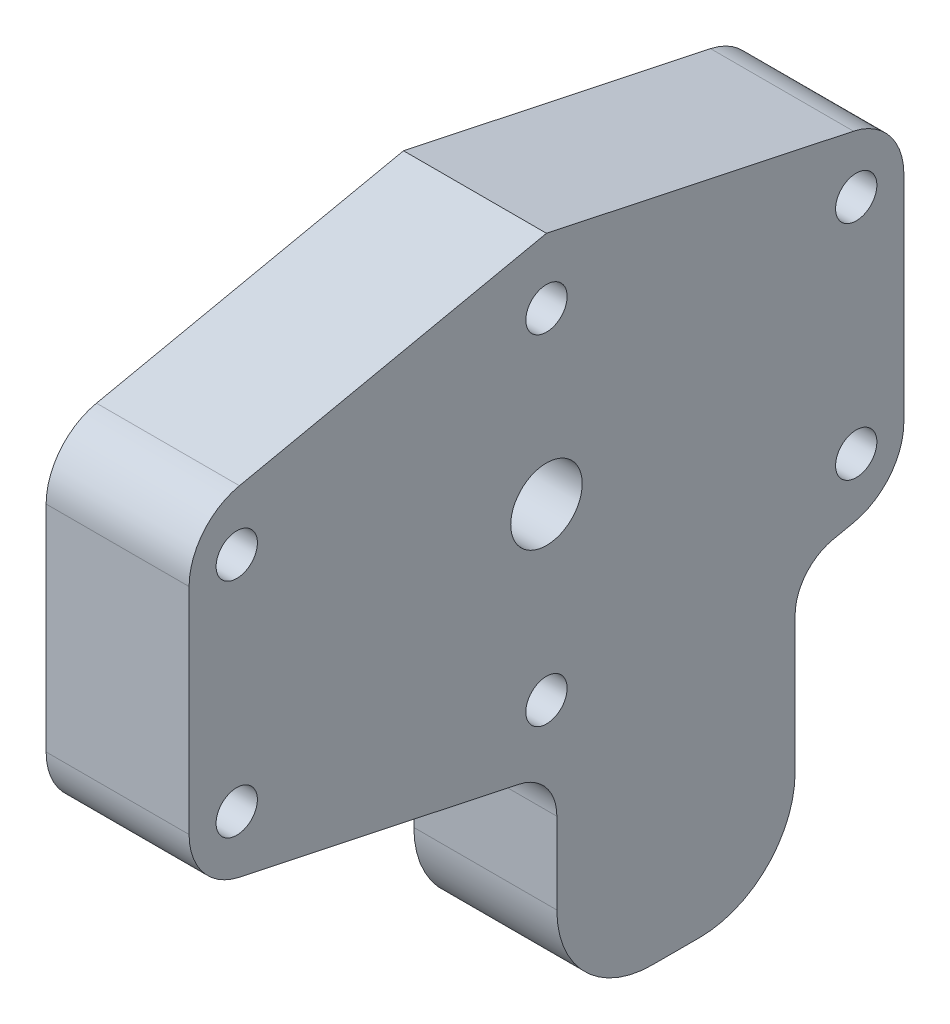
SolidWorks part; units mm, degrees
ref_plane "Front" through (0, 0, 0) normal (0, 0, 1) x (1, 0, 0)
ref_plane "Top" through (0, 0, 0) normal (0, 1, 0) x (1, 0, 0)
ref_plane "Right" through (0, 0, 0) normal (1, 0, 0) x (0, 0, -1)
sketch "Sketch1" plane through (0, 0, 0) normal (1, 0, 0) x (0, 0, -1)
  line L0 (0, -20) -> (22.5, -24.7697)
  line L1 (0, 0) -> (45, 0)
  line L2 (0, 0) -> (0, -20)
  line L3 (0, -20) -> (45, -20)
  line L4 (45, 0) -> (45, -20)
  line L5 (22.5, -24.7697) -> (45, -20)
  line L6 (22.5, 4.7697) -> (0, 0)
  line L7 (22.5, 4.7697) -> (45, 0)
  circle A0 centre (22.5, -20.6808) radius 1.3
  circle A1 centre (22.5, 0.6808) radius 1.3
  circle A2 centre (42, -17) radius 1.3
  circle A3 centre (3, -17) radius 1.3
  circle A4 centre (3, -3) radius 1.3
  circle A5 centre (42, -3) radius 1.3
  dimension "D7" = 2.6
  dimension "D8" = 2.6
  dimension "D13" = 2.6
  dimension "D1" = 45
  dimension "D2" = 20
  dimension "D3" = 23
  dimension "D4" = 23
  dimension "D5" = 23
  dimension "D6" = 23
  dimension "D9" = 4
  dimension "D10" = 4
  dimension "D11" = 4
  dimension "D12" = 4
  dimension "D14" = 3
  dimension "D15" = 3
  dimension "D16" = 2
  dimension "D17" = 2
extrude "Boss-Extrude1" add sketch "Sketch1" along normal blind 9 contours L7 L6 L1 A1 | L4 L1 L2 L3 | L0 L5 L3 A0 region at (0, -20.4525, -10.6963) region at (0, -10, -22.5) region at (0, 1.9422, -11.3438)
sketch "Sketch7" plane through (0, 0, 0) normal (-1, 0, 0) x (0, 0, 1)
  line L0 (-41.7, -10) -> (-31.3, -10)
  line L1 (-45, 0) -> (-45, -20) construction
  line L2 (-13.7, -10) -> (-3.3, -10)
  arc A0 (-31.3, -10) -> (-41.7, -10) centre (-36.5, -10) ccw
  arc A1 (-3.3, -10) -> (-13.7, -10) centre (-8.5, -10) ccw
  dimension "D1" = 10.4
  dimension "D2" = 8.5
  dimension "D3" = 10
  dimension "D4" = 2
revolve "Cut-Revolve3" cut sketch "Sketch7" angle 180 about L0 reverse direction yes
sketch "Sketch8" plane through (0, 0, 0) normal (-1, 0, 0) x (0, 0, 1)
  circle A0 centre (-22.5, -10) radius 8.1
  dimension "D1" = 16.2
  dimension "D2" = 22.5
  dimension "D3" = 10
extrude "Cut-Extrude4" cut sketch "Sketch8" against normal blind 5.5
sketch "Sketch9" plane through (5.5, 0, 0) normal (-1, 0, 0) x (0, 0, 1)
  circle A0 centre (-22.5, -10) radius 2.25
  dimension "D1" = 4.5
extrude "Cut-Extrude5" cut sketch "Sketch9" against normal through all
sketch "Sketch16" plane through (9, 0, 0) normal (1, 0, 0) x (0, 0, -1)
  line L0 (38.1522, -21.4516) -> (38.1522, -38.4516)
  line L1 (22.5, -24.7697) -> (45, -20) construction
  line L2 (38.1522, -38.4516) -> (23.1522, -38.4516)
  line L3 (23.1522, -38.4516) -> (23.1522, -24.6314)
  line L4 (23.1522, -24.6314) -> (38.1522, -21.4516)
  dimension "D1" = 17
  dimension "D2" = 15
  dimension "D3" = 7
extrude "Boss-Extrude7" add sketch "Sketch16" against normal blind 9
sketch "Sketch17" plane through (0, 0, 0) normal (-1, 0, 0) x (0, 0, 1)
  line L0 (-38.1522, -38.4516) -> (-38.1522, -21.4516) construction
  line L1 (-23.1522, -38.4516) -> (-38.1522, -38.4516) construction
  line L2 (-25.4522, -30.4516) -> (-35.8522, -30.4516)
  arc A0 (-25.4522, -30.4516) -> (-35.8522, -30.4516) centre (-30.6522, -30.4516) ccw
  dimension "D1" = 10.4
  dimension "D2" = 7.5
  dimension "D3" = 8
revolve "Cut-Revolve4" cut sketch "Sketch17" angle 180 about L2
fillet "Fillet1" radius 6 2 edges at (4.5, -38.4516, -23.1522) (4.5, -38.4516, -38.1522)
fillet "Fillet2" radius 4 4 edges at (4.5, -20, -45) (4.5, 0, -45) (4.5, 0, 0) (4.5, -20, 0)
fillet "Fillet3" radius 3 2 edges at (4.5, -21.4516, -38.1522) (4.5, -24.6314, -23.1522)
fillet "Fillet4" radius 3 1 edges at (4.5, -24.7697, -22.5)
